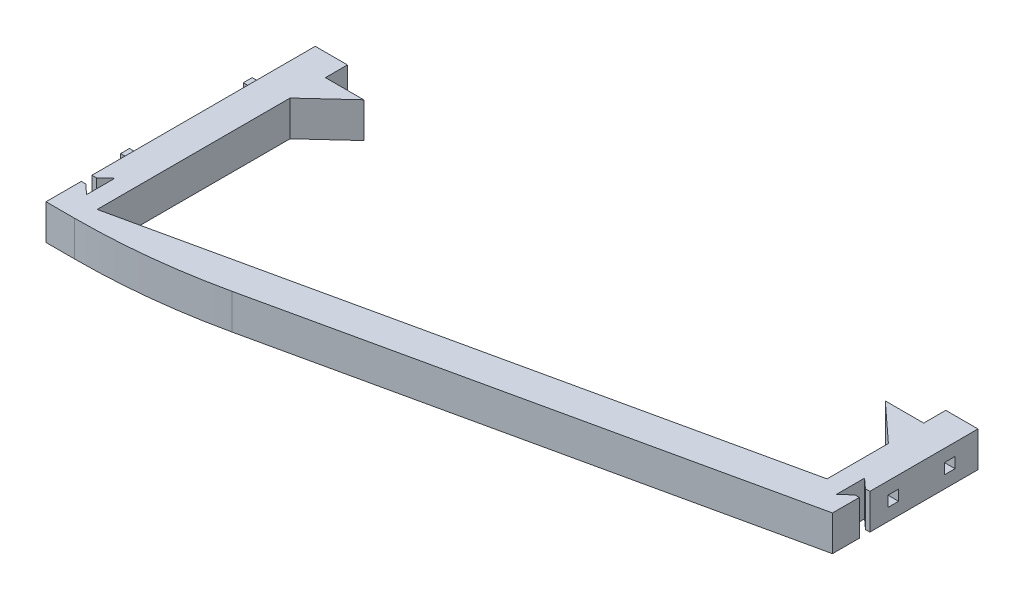
SolidWorks part; units mm, degrees
ref_plane "Přední rovina" through (0, 0, 0) normal (0, 0, 1) x (1, 0, 0)
ref_plane "Horní rovina" through (0, 0, 0) normal (0, 1, 0) x (1, 0, 0)
ref_plane "Pravá rovina" through (0, 0, 0) normal (1, 0, 0) x (0, 0, -1)
sketch "Skica1" plane through (0, 0, 0) normal (0, 1, 0) x (1, 0, 0)
  line L0 (0, 0) -> (0, -66)
  line L1 (0, -66) -> (150.15, -32.9681)
  line L2 (150.15, -32.9681) -> (150.15, 0)
  line L3 (150.15, 0) -> (142.85, 0)
  line L4 (142.85, 0) -> (142.85, -26.8948)
  line L5 (142.85, -26.8948) -> (7.3, -56.7147)
  line L6 (7.3, -56.7147) -> (7.3, 0)
  line L7 (7.3, 0) -> (0, 0)
  dimension "D1" = 7.3
  dimension "D2" = 7.3
  dimension "D3" = 66
  dimension "D4" = 7.5
  dimension "D5" = 150.15
  dimension "D6" = 77.593
extrude "Přidat vysunutím1" add sketch "Skica1" along normal blind 8
sketch "Skica2" plane through (0, 8, 0) normal (0, 1, 0) x (1, 0, 0)
  line L5 (0, -50.6) -> (1, -50.6)
  line L6 (0, 0) -> (0, -66) construction
  line L7 (1, -50.6) -> (3.2, -48.6)
  line L8 (3.2, -48.6) -> (3.2, -55)
  line L9 (3.2, -55) -> (1, -53)
  line L10 (1, -53) -> (0, -53)
  line L11 (0, -53) -> (0, -50.6)
  dimension "D1" = 6.4
  dimension "D2" = 2.4
  dimension "D3" = 1
  dimension "D4" = 1
  dimension "D5" = 2
  dimension "D6" = 3.2
  dimension "D7" = 11
extrude "Odebrat vysunutím1" cut sketch "Skica2" against normal through all
sketch "Skica3" plane through (0, 0, 0) normal (-1, 0, 0) x (0, 0, 1)
  line L0 (0, 8) -> (0, 0) construction
  line L1 (10.3, 5) -> (12.3, 5)
  line L2 (10.3, 5) -> (10.3, 3)
  line L3 (10.3, 3) -> (12.3, 3)
  line L4 (12.3, 5) -> (12.3, 3)
  line L5 (38.1, 5) -> (40.1, 5)
  line L6 (38.1, 5) -> (38.1, 3)
  line L7 (38.1, 3) -> (40.1, 3)
  line L8 (40.1, 5) -> (40.1, 3)
  line L17 (0, 8) -> (50.6, 8) construction
  point P16 (10.3, 4)
  dimension "D1" = 10.3
  dimension "D2" = 2
  dimension "D3" = 2
  dimension "D4" = 3
  dimension "D5" = 2
  dimension "D6" = 2
  dimension "D7" = 3
  dimension "D8" = 25.8
extrude "Přidat vysunutím2" add sketch "Skica3" along normal blind 4
sketch "Skica5" plane through (0, 8, 0) normal (0, 1, 0) x (1, 0, 0)
  line L0 (0, 0) -> (0, -50.6) construction
  line L1 (0, -5) -> (16, -5)
  line L2 (0, -5) -> (0, -13)
  line L3 (0, -13) -> (16, -13)
  line L4 (16, -5) -> (16, -13)
  line L5 (150.15, -32.9681) -> (150.15, 0) construction
  line L6 (150.15, -5) -> (134.15, -5)
  line L7 (150.15, -5) -> (150.15, -13)
  line L8 (150.15, -13) -> (134.15, -13)
  line L9 (134.15, -5) -> (134.15, -13)
  line L10 (150.15, 0) -> (142.85, 0) construction
  line L11 (7.3, 0) -> (0, 0) construction
  dimension "D1" = 8
  dimension "D2" = 8
  dimension "D3" = 16
  dimension "D4" = 16
  dimension "D5" = 5
  dimension "D6" = 5
extrude "Přidat vysunutím3" add sketch "Skica5" against normal blind 8
sketch "Skica7" plane through (0, 0, 0) normal (0, -1, 0) x (1, 0, 0)
  line L0 (7.3, 13) -> (16, 5)
  line L1 (16, 5) -> (16, 13)
  line L2 (16, 13) -> (7.3, 13)
  line L3 (134.15, 5) -> (134.15, 13)
  line L4 (134.15, 13) -> (142.85, 13)
  line L5 (142.85, 13) -> (134.15, 5)
extrude "Odebrat vysunutím4" cut sketch "Skica7" against normal through all
sketch "Skica4" plane through (150.15, 0, 0) normal (1, 0, 0) x (0, 0, -1)
  line L0 (-32.9681, 8) -> (0, 8) construction
  line L5 (-20.4, 5.2) -> (-18, 5.2)
  line L6 (-20.4, 5.2) -> (-20.4, 2.8)
  line L7 (-20.4, 2.8) -> (-18, 2.8)
  line L8 (-18, 5.2) -> (-18, 2.8)
  line L9 (-7.6, 5.2) -> (-5.2, 5.2)
  line L10 (-7.6, 5.2) -> (-7.6, 2.8)
  line L11 (-7.6, 2.8) -> (-5.2, 2.8)
  line L12 (-5.2, 5.2) -> (-5.2, 2.8)
  line L14 (0, 8) -> (0, 0) construction
  point P16 (-18, 4)
  dimension "D1" = 2.4
  dimension "D2" = 2.4
  dimension "D3" = 2.8
  dimension "D7" = 2.4
  dimension "D8" = 2.4
  dimension "D9" = 2.8
  dimension "D10" = 5.2
  dimension "D12" = 10.4
extrude "Odebrat vysunutím2" cut sketch "Skica4" against normal blind 4.4
sketch "Skica8" plane through (0, 8, 0) normal (0, 1, 0) x (1, 0, 0)
  line L6 (150.15, -24.5) -> (149.15, -24.5)
  line L7 (150.15, -32.9681) -> (150.15, 0) construction
  line L8 (149.15, -24.5) -> (146.95, -22.5)
  line L9 (146.95, -22.5) -> (146.95, -28.9)
  line L10 (146.95, -28.9) -> (149.15, -26.9)
  line L11 (150.15, -26.9) -> (150.15, -24.5)
  line L12 (149.15, -26.9) -> (150.15, -26.9)
  line L13 (150.15, 0) -> (142.85, 0) construction
  point P10 (146.5, 0)
  dimension "D1" = 6.4
  dimension "D2" = 1
  dimension "D3" = 2.4
  dimension "D4" = 2
  dimension "D5" = 3.2
  dimension "D6" = 22.5
  dimension "D7" = 1
extrude "Odebrat vysunutím5" cut sketch "Skica8" against normal through all
sketch "Skica9" plane through (0, 8, 0) normal (0, 1, 0) x (1, 0, 0)
  line L0 (0, -61) -> (22.7281, -61)
  line L1 (0, -53) -> (0, -66) construction
  line L2 (0, -66) -> (150.15, -32.9681) construction
  line L3 (22.7281, -61) -> (0, -66)
  line L4 (0, -66) -> (0, -61)
  dimension "D1" = 5
extrude "Odebrat vysunutím6" cut sketch "Skica9" against normal through all
fillet "Zaoblit1" radius 150 1 edges at (22.7281, 4, 61)
